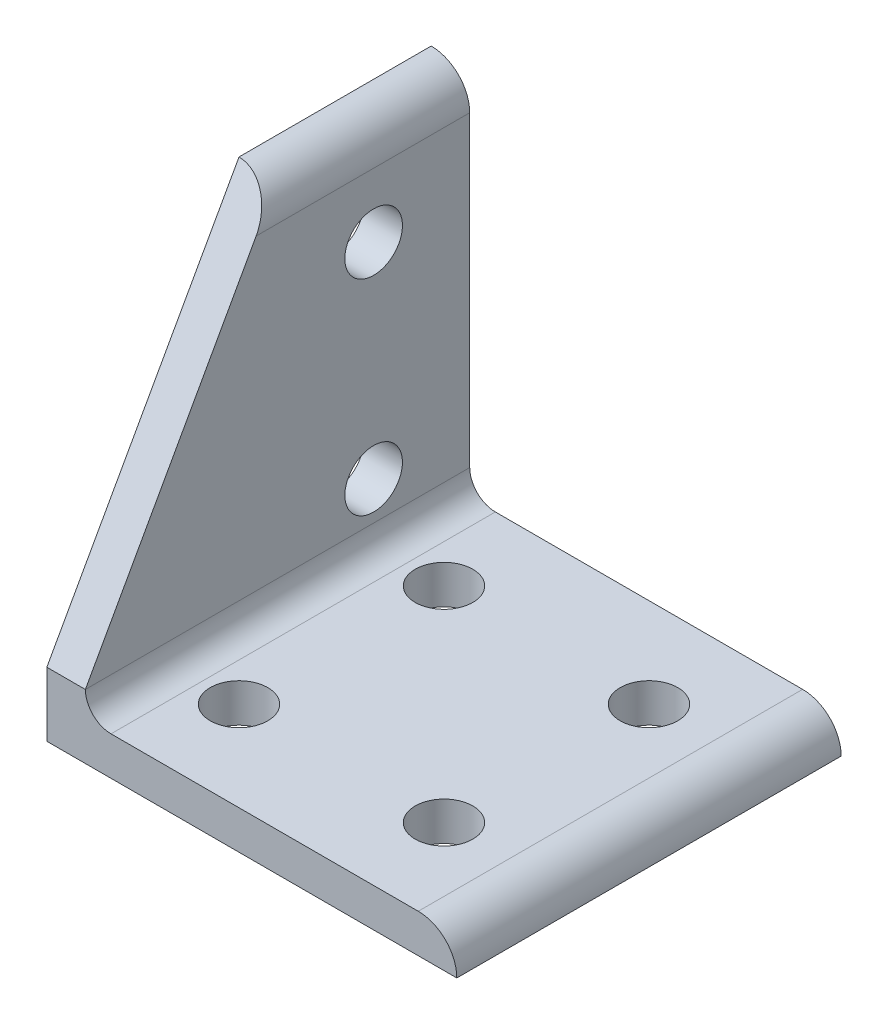
SolidWorks part; units mm, degrees
ref_plane "Front Plane" through (0, 0, 0) normal (0, 0, 1) x (1, 0, 0)
ref_plane "Top Plane" through (0, 0, 0) normal (0, 1, 0) x (1, 0, 0)
ref_plane "Right Plane" through (0, 0, 0) normal (1, 0, 0) x (0, 0, -1)
sketch "Sketch1" plane through (0, 0, 0) normal (0, 0, 1) x (1, 0, 0)
  line L0 (25.4, -25.4) -> (-25.4, -25.4) construction
  line L1 (-25.4, 25.4) -> (-25.4, -25.4) construction
  line L2 (25.4, -25.4) -> (25.4, -20.6248) construction
  point P3 (0, -25.4)
  point P6 (-25.4, 0)
  dimension "Length" = 50.8
  dimension "Thickness" = 4.7752
sketch "Sketch2" plane through (0, 0, 0) normal (1, 0, 0) x (0, 0, -1)
  line L0 (23.8125, 0) -> (-23.8125, 0) construction
  line L1 (0, 25.4) -> (23.8125, 25.4) construction
  line L2 (11.9062, 25.4) -> (11.9062, 12.7) construction
  line L3 (8.3375, 12.7) -> (15.475, 12.7) construction
  point P10 (0, 0)
  point P13 (0, 25.4)
  point P19 (11.9062, 12.7)
  dimension "Width" = 47.625
  dimension "Hole Dia" = 7.1374
  dimension "Hole Spacing" = 25.4
sketch "Sketch3" plane through (0, 0, 0) normal (0, 1, 0) x (1, 0, 0)
  line L1 (25.4, 0) -> (-25.4, 0) construction
  line L2 (25.4, 0) -> (-25.4, 0) construction
  point P0 (-12.7, 12.7)
  dimension "Hole to Edge" = 12.7
sketch "Sketch4" plane through (0, 0, 0) normal (0, 0, 1) x (1, 0, 0)
  line L0 (-25.4, 25.4) -> (-25.4, -25.4)
  line L1 (-25.4, -25.4) -> (25.4, -25.4)
  line L2 (-20.6248, 20.6248) -> (-20.6248, -17.4498)
  line L3 (-17.4498, -20.6248) -> (20.6248, -20.6248)
  arc A0 (-20.6248, -17.4498) -> (-17.4498, -20.6248) centre (-17.4498, -17.4498) ccw
  arc A1 (20.6248, -20.6248) -> (25.4, -25.4) centre (20.6248, -25.4) cw
  arc A2 (-20.6248, 20.6248) -> (-25.4, 25.4) centre (-25.4, 20.6248) ccw
  dimension "Radius" = 3.175
extrude "Boss-Extrude1" add sketch "Sketch4" against normal up to vertex (23.8125 mm away) and the other way up to vertex (23.8125 mm away) up to point (0, 0, -23.8125) other way up to point (0, 0, 23.8125)
sketch "Sketch5" plane through (-20.6248, 0, 0) normal (1, 0, 0) x (0, 0, -1)
  line L14 (0, 25.4) -> (-23.8125, 25.4)
  line L15 (-23.8125, 25.4) -> (-23.8125, 20.6248) construction
  line L16 (-23.8125, 25.4) -> (-23.8125, -17.4498)
  line L17 (-23.8125, -17.4498) -> (0, 25.4)
extrude "Cut-Extrude1" cut sketch "Sketch5" against normal through all both and the other way through all
sketch "Sketch6" plane through (-20.6248, 0, 0) normal (1, 0, 0) x (0, 0, -1)
  line L0 (8.3375, 12.7) -> (15.475, 12.7) construction
  line L1 (23.8125, 0) -> (-23.8125, 0) construction
  line L2 (23.8125, 0) -> (-23.8125, 0) construction
  circle A0 centre (11.9063, 12.7) radius 3.5687
  circle A1 centre (11.9063, -12.7) radius 3.5687
extrude "Cut-Extrude2" cut sketch "Sketch6" against normal through all
sketch "Sketch7" plane through (0, -20.6248, 0) normal (0, 1, 0) x (1, 0, 0)
  line L0 (25.4, 0) -> (-25.4, 0) construction
  line L1 (25.4, 0) -> (-25.4, 0) construction
  circle A0 centre (-12.7, 12.7) radius 3.5687
  circle A1 centre (12.7, 12.7) radius 3.5687
  circle A2 centre (12.7, -12.7) radius 3.5687
  circle A3 centre (-12.7, -12.7) radius 3.5687
  dimension "D1" = 7.1374
  dimension "D2" = 25.4
extrude "Cut-Extrude3" cut sketch "Sketch7" against normal through all
equation "\"D1@Sketch3\" = \"Hole Spacing@Sketch2\""
equation "\"D1@Sketch7\"=\"Hole Dia@Sketch2\""
equation "\"D2@Sketch7\"=\"Hole Spacing@Sketch2\""
